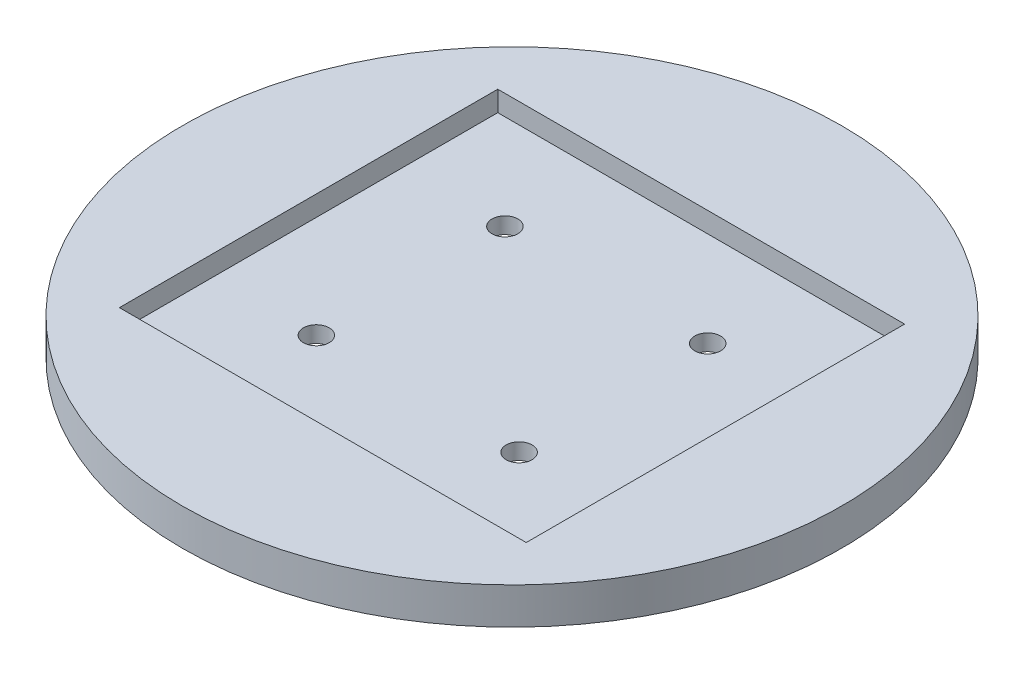
SolidWorks part; units mm, degrees
ref_plane "Front Plane" through (0, 0, 0) normal (0, 0, 1) x (1, 0, 0)
ref_plane "Top Plane" through (0, 0, 0) normal (0, 1, 0) x (1, 0, 0)
ref_plane "Right Plane" through (0, 0, 0) normal (1, 0, 0) x (0, 0, -1)
sketch "Sketch1" plane through (0, 0, 0) normal (0, 1, 0) x (1, 0, 0)
  line L0 (-59, 55.5) -> (-59, -55.5)
  line L1 (-50, 46.5) -> (50, 46.5)
  line L2 (-50, 46.5) -> (-50, -46.5)
  line L3 (-50, -46.5) -> (50, -46.5)
  line L4 (50, 46.5) -> (50, -46.5)
  line L5 (-50, 46.5) -> (50, -46.5) construction
  line L6 (-50, -46.5) -> (50, 46.5) construction
  line L7 (-59, -55.5) -> (59, -55.5)
  line L8 (59, 55.5) -> (59, -55.5)
  line L9 (-59, 55.5) -> (59, 55.5)
  circle A0 centre (0, 0) radius 81.0015
  point P0 (0, 0)
  dimension "D4" = 162.0031
  dimension "D1" = 100
  dimension "D2" = 93
  dimension "D3" = 9
extrude "Boss-Extrude1" add sketch "Sketch1" along normal blind 9 contours L4 L1 L2 L3 | L9 L0 L7 L8 L1 L4 L3 L2 | L0 A0 | L7 A0 | L8 A0 | L9 A0 region at (0, 0, -53.88) region at (0, 0, -65.8521) region at (-67.9118, 0, 0) region at (0, 0, 65.8521) region at (67.9118, 0, 0) region at (0, 0, 0)
sketch "Sketch2" plane through (0, 9, 0) normal (0, 1, 0) x (1, 0, 0)
  line L0 (-50, 0) -> (50, 0) construction
  line L1 (-50, -46.5) -> (50, -46.5)
  line L2 (-50, -46.5) -> (-50, 46.5)
  line L3 (-50, 46.5) -> (50, 46.5)
  line L4 (50, -46.5) -> (50, 46.5)
  line L5 (-50, -46.5) -> (50, 46.5) construction
  line L6 (-50, 46.5) -> (50, -46.5) construction
  line L7 (-50, 0) -> (0, -46.5) construction
  line L8 (0, 46.5) -> (0, -46.5) construction
  circle A0 centre (-24.9196, -23.1752) radius 3.175
  circle A1 centre (24.9196, -23.1752) radius 3.175
  circle A2 centre (24.9196, 23.1752) radius 3.175
  circle A3 centre (-24.9196, 23.1752) radius 3.175
  dimension "D1" = 6.35
  dimension "D2" = 49.8391
  dimension "D4" = 46.3504
  dimension "D3" = 100
extrude "Cut-Extrude1" cut sketch "Sketch2" against normal blind 5 contours L1 L4 | L2 L1 | L3 L2 | L4 L3 region at (0, 9, 0)
extrude "Cut-Extrude2" cut sketch "Sketch2<3>" against normal through all contours A0 | A1 | A2 | A3
sketch "Sketch2<3>" plane through (0, 9, 0) normal (0, 1, 0) x (1, 0, 0) same geometry as "Sketch2"
